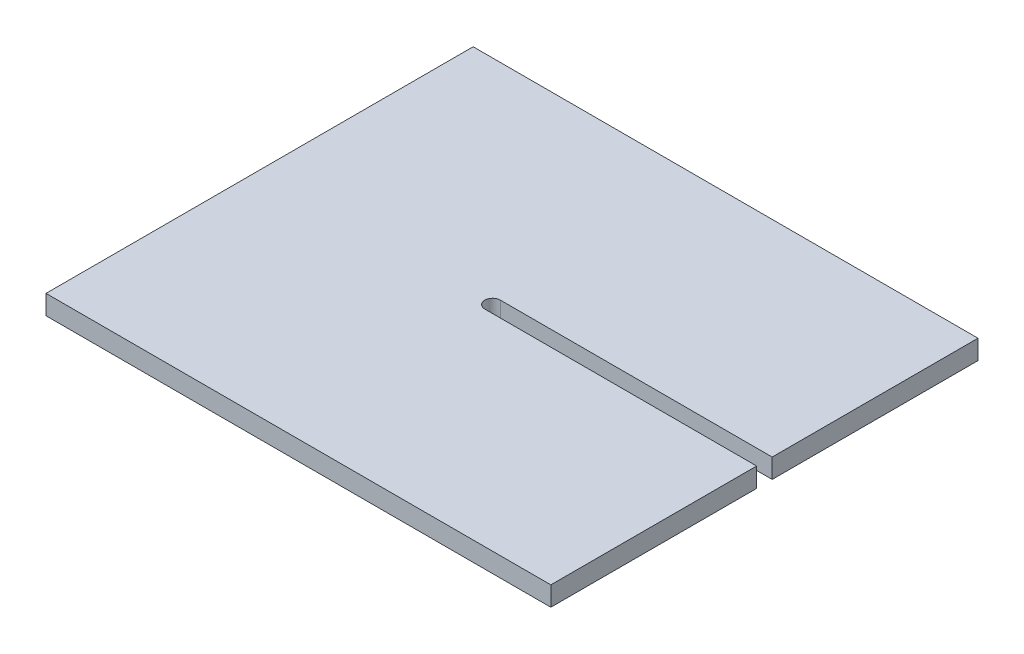
SolidWorks part; units mm, degrees
material "Ceramic Porcelain"
ref_plane "Front Plane" through (0, 0, 0) normal (0, 0, 1) x (1, 0, 0)
ref_plane "Top Plane" through (0, 0, 0) normal (0, 1, 0) x (1, 0, 0)
ref_plane "Right Plane" through (0, 0, 0) normal (1, 0, 0) x (0, 0, -1)
sketch "Sketch1" plane through (0, 0, 0) normal (1, 0, 0) x (0, 0, -1)
  line L1 (-44.1628, -6.0661) -> (25.6872, -6.0661)
  line L2 (-44.1628, -6.0661) -> (-44.1628, -9.2411)
  line L3 (-44.1628, -9.2411) -> (25.6872, -9.2411)
  line L4 (25.6872, -6.0661) -> (25.6872, -9.2411)
  dimension "D1" = 3.175
  dimension "D2" = 69.85
extrude "Boss-Extrude2" add sketch "Sketch1" along normal blind 82.55
sketch "Sketch2" plane through (0, -6.0661, 0) normal (0, 1, 0) x (1, 0, 0)
  line L0 (38.1, -7.9678) -> (82.55, -7.9678)
  line L1 (82.55, 25.6872) -> (82.55, -44.1628) construction
  line L2 (82.55, -7.9678) -> (82.55, -10.5078)
  line L3 (82.55, -10.5078) -> (38.1, -10.5078)
  line L4 (38.1, -9.2378) -> (0, -9.2378) construction
  line L5 (0, 25.6872) -> (0, -44.1628) construction
  arc A0 (38.1, -7.9678) -> (38.1, -10.5078) centre (38.1, -9.2378) ccw
  dimension "D1" = 2.54
  dimension "D2" = 38.1
extrude "Cut-Extrude1" cut sketch "Sketch2" against normal through all
